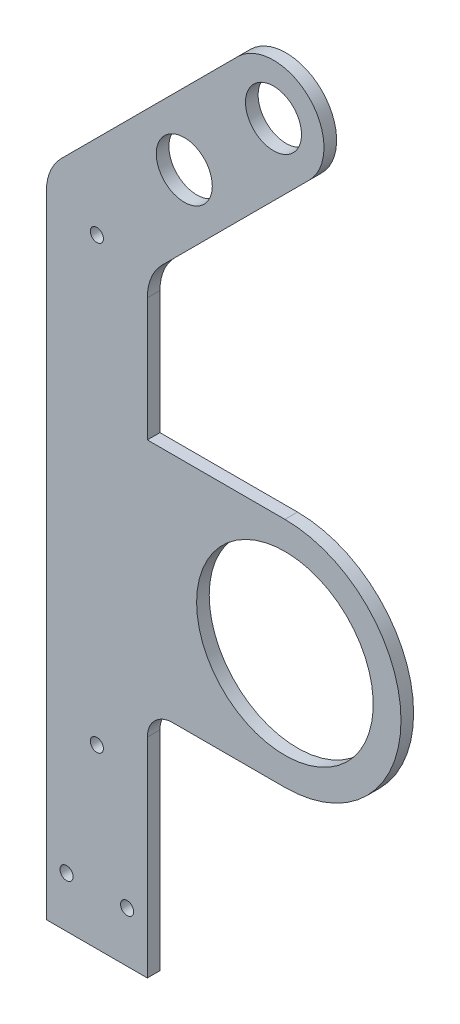
SolidWorks part; units mm, degrees
material "6061 合金"
ref_plane "前视基准面" through (0, 0, 0) normal (0, 0, 1) x (1, 0, 0)
ref_plane "上视基准面" through (0, 0, 0) normal (0, 1, 0) x (1, 0, 0)
ref_plane "右视基准面" through (0, 0, 0) normal (1, 0, 0) x (0, 0, -1)
other "Configuration Table"
sketch "草图1" plane through (0, 0, 0) normal (0, 0, 1) x (1, 0, 0)
  circle A0 centre (0, 0) radius 20
  circle A1 centre (0, 0) radius 11.1
  dimension "D1" = 40
  dimension "D2" = 22.2
extrude "凸台-拉伸1" add sketch "草图1" along normal blind 60 contours A1 | A0 region at (0, 0, 0)
ref_plane "基准面1" through (0, 0, 30) normal (0, 0, 1) x (1, 0, 0)
sketch "草图2" plane through (0, 0, 30) normal (0, 0, 1) x (1, 0, 0)
  line L0 (0, 0) -> (-70, -70) construction
  line L1 (-70, -70) -> (-70, -320) construction
  line L2 (0, -57.3148) -> (0, 49.9409) construction
  line L3 (-56.8582, 0) -> (46.4003, 0) construction
  line L4 (-14.1421, 14.1421) -> (-90, -61.7157)
  line L5 (14.1421, -14.1421) -> (-50, -78.2843)
  line L6 (-90, -61.7157) -> (-90, -320)
  line L7 (-50, -78.2843) -> (-50, -320)
  line L8 (-90, -320) -> (-50, -320)
  circle A2 centre (0, 0) radius 20 construction
  arc A3 (-14.1421, 14.1421) -> (14.1421, -14.1421) centre (0, 0) ccw
  dimension "D1" = 45
  dimension "D2" = 250
  dimension "D3" = 70
  dimension "D4" = 40
  dimension "D5" = 40
extrude "凸台-拉伸2" add sketch "草图2" along normal mid plane 60 contours L7 L8 L6 L4 A3 L5
sketch "草图4" plane through (0, 0, 60) normal (0, 0, 1) x (1, 0, 0)
  line L0 (-90, -61.7157) -> (-90, -320) construction
  line L1 (-90, -290) -> (-50, -290)
  line L2 (-90, -290) -> (-90, -350)
  line L4 (-50, -290) -> (-50, -350)
  line L5 (-50, -78.2843) -> (-50, -320) construction
  line L6 (-90, -320) -> (-50, -320) construction
  arc A0 (-90, -350) -> (-50, -350) centre (-70, -350) ccw
  circle A1 centre (-70, -350) radius 11
  dimension "D3" = 22
  dimension "D1" = 30
  dimension "D2" = 30
extrude "凸台-拉伸3" add sketch "草图4" along normal blind 5
mirror "镜向1" about plane through (0, 0, 30) normal (0, 0, 1) of "凸台-拉伸3"
sketch "草图5" plane through (0, 0, 0) normal (0, 1, 0) x (1, 0, 0)
  line L0 (0, 0) -> (0, -78.0582) construction
ref_plane "基准面2" through (-70, 0, 0) normal (-1, 0, 0) x (0, 0, 1)
sketch "草图7" plane through (-70, 0, 0) normal (-1, 0, 0) x (0, 0, 1)
  line L0 (-34.1239, -350) -> (109.535, -350) construction
sketch "草图8" plane through (0, 0, 60) normal (0, 0, 1) x (1, 0, 0)
  line L0 (0, 0) -> (-70, -70) construction
  circle A0 centre (-35.3553, -35.3553) radius 11.1
  dimension "D1" = 22.2
  dimension "D2" = 50
extrude "切除-拉伸1" cut sketch "草图8" against normal blind 100
fillet "圆角4" radius 20 2 edges at (-90, -61.7157, 30) (-50, -78.2843, 30)
fillet "圆角1" [suppressed] radius 50
fillet "圆角2" [suppressed] radius 3
sketch "草图9" plane through (0, 0, 65) normal (0, 0, 1) x (1, 0, 0)
  circle A0 centre (-70, -350) radius 13
  dimension "D1" = 26
extrude "切除-拉伸2" [suppressed] cut sketch "草图9" against normal blind 0.75
sketch "草图10" plane through (0, 0, -5) normal (0, 0, -1) x (-1, 0, 0)
  circle A0 centre (70, -350) radius 13
  dimension "D1" = 26
extrude "切除-拉伸3" [suppressed] cut sketch "草图10" against normal blind 0.75 contours A0
sketch "草图11" plane through (-90, 0, 0) normal (-1, 0, 0) x (0, 0, 1)
  circle A0 centre (48.5, -118.9949) radius 2.75
  circle A1 centre (48.5, -183.9949) radius 2.75
  circle A2 centre (48.5, -248.9949) radius 2.75
  circle A3 centre (11.5, -248.9949) radius 2.75
  circle A4 centre (11.5, -183.9949) radius 2.75
  circle A5 centre (11.5, -118.9949) radius 2.75
  dimension "D1" = 5.5
extrude "切除-拉伸4" [suppressed] cut sketch "草图11" against normal through all contours A1 | A2 | A0 | A3 | A4 | A5
sketch "草图12" [suppressed] plane through (-90, 0, 0) normal (-1, 0, 0) x (0, 0, 1)
  line L0 (30, -62.0134) -> (30, -339.6946) construction
  line L1 (10, -128.9949) -> (50, -128.9949)
  line L2 (10, -128.9949) -> (10, -173.9949)
  line L3 (10, -173.9949) -> (50, -173.9949)
  line L4 (50, -128.9949) -> (50, -173.9949)
  line L5 (10, -193.9949) -> (50, -193.9949)
  line L6 (10, -193.9949) -> (10, -238.9949)
  line L7 (10, -238.9949) -> (50, -238.9949)
  line L8 (50, -193.9949) -> (50, -238.9949)
  line L9 (10, -258.9949) -> (50, -258.9949)
  line L10 (10, -258.9949) -> (10, -290)
  line L11 (10, -290) -> (50, -290)
  line L12 (50, -258.9949) -> (50, -290)
  line L13 (19.5, -173.9949) -> (40.5, -173.9949)
  line L14 (19.5, -173.9949) -> (19.5, -193.9949)
  line L15 (19.5, -193.9949) -> (40.5, -193.9949)
  line L16 (40.5, -173.9949) -> (40.5, -193.9949)
  line L17 (19.5, -238.9949) -> (40.5, -238.9949)
  line L18 (19.5, -238.9949) -> (19.5, -258.9949)
  line L19 (19.5, -258.9949) -> (40.5, -258.9949)
  line L20 (40.5, -238.9949) -> (40.5, -258.9949)
  line L21 (60, -82.4264) -> (60, -290) construction
  line L22 (0, -290) -> (0, -82.4264) construction
  line L23 (57, -320) -> (3, -320) construction
  circle A0 centre (48.5, -118.9949) radius 2.75 construction
  circle A1 centre (48.5, -183.9949) radius 2.75 construction
  circle A2 centre (48.5, -248.9949) radius 2.75 construction
  dimension "D1" = 10
  dimension "D2" = 10
  dimension "D3" = 10
  dimension "D4" = 8
  dimension "D5" = 10
  dimension "D6" = 10
  dimension "D7" = 10
  dimension "D8" = 30
extrude "减重" [suppressed] cut sketch "草图12" against normal through all contours L0 L1 L2 L3 | L15 L0 L17 L7 L8 L5 | L0 L5 L6 L7 | L19 L0 L11 L12 L9 | L0 L9 L10 L11 | L1 L0 L13 L3 L4
fillet "圆角3" [suppressed] radius 3
sketch "草图13" plane through (0, 0, 60) normal (0, 0, 1) x (1, 0, 0)
  circle A0 centre (0, 0) radius 13
  circle A1 centre (-35.3553, -35.3553) radius 13
  dimension "D1" = 26
  dimension "D2" = 26
extrude "切除-拉伸6" [suppressed] cut sketch "草图13" against normal blind 1.75
sketch "草图14" plane through (0, 0, 0) normal (0, 0, -1) x (-1, 0, 0)
  circle A0 centre (0, 0) radius 13
  circle A1 centre (35.3553, -35.3553) radius 13
  dimension "D1" = 26
  dimension "D2" = 26
extrude "切除-拉伸7" [suppressed] cut sketch "草图14" against normal blind 1.75
sketch "草图15" [suppressed] plane through (0, 0, 0) normal (0, 0, -1) x (-1, 0, 0)
  line L0 (0, 0) -> (70, -350) construction
  line L1 (56.2719, -67.2005) -> (60.1942, -86.8121) construction
  line L2 (70, -350) -> (204.3541, -323.1292) construction
  circle A0 centre (56.2719, -67.2005) radius 2.75
  circle A1 centre (75.2172, -73.6095) radius 2.75
  circle A2 centre (60.1942, -86.8121) radius 2.75
  dimension "D1" = 5.5
  dimension "D2" = 20
  dimension "D3" = 20
  dimension "D4" = 20
  dimension "D5" = 42
  dimension "D6" = 270
extrude "切除-拉伸8" [suppressed] cut sketch "草图15" against normal through all contours A2 | A0 | A1
ref_plane "小腿主干连杆面" through (0, 0, 0) normal (0.9806, -0.1961, 0) x (0, 0, -1)
ref_plane "小腿主干对称面" through (0, 0, 30) normal (0, 0, -1) x (-1, 0, 0)
sketch "草图16" plane through (0, 0, 60) normal (0, 0, 1) x (1, 0, 0)
  line L0 (0, 0) -> (-70, -350)
  line L1 (-35.3553, -35.3553) -> (0, 0)
sketch "草图17" plane through (0, 0, 60) normal (0, 0, 1) x (1, 0, 0)
  line L0 (0, 0) -> (-70, -350) construction
  line L1 (118.6974, 32.5948) -> (32.9122, -396.3312) construction
  line L2 (92.7764, -97.0102) -> (24.1357, -83.2821)
  line L3 (73.1648, -195.0683) -> (4.5241, -181.3401)
  circle A0 centre (24.1357, -83.2821) radius 46
  circle A1 centre (4.5241, -181.3401) radius 46
  dimension "D3" = 92
  dimension "D4" = 92
  dimension "D1" = 110
  dimension "D2" = 70
  dimension "D5" = 180
  dimension "D6" = 280
sketch "草图18" plane through (0, 0, 60) normal (0, 0, 1) x (1, 0, 0)
  line L1 (14.1421, -14.1421) -> (-44.1421, -72.4264) construction
  line L3 (14.1421, -14.1421) -> (-44.1421, -72.4264)
  line L4 (16.784, -10.8765) -> (56.6627, -50.7551)
  line L5 (-50, -129.2821) -> (24.1357, -129.2821)
  line L10 (-90, -290) -> (-50, -290)
  line L11 (-50, -290) -> (-50, -86.5685)
  line L12 (-44.1421, -72.4264) -> (14.1421, -14.1421)
  line L13 (-14.1421, 14.1421) -> (-84.1421, -55.8579)
  line L14 (-90, -70) -> (-90, -290)
  line L16 (-50, -129.2821) -> (-50, -86.5685)
  line L17 (-44.1421, -72.4264) -> (14.1421, -14.1421)
  circle A0 centre (24.1357, -83.2821) radius 46 construction
  arc A1 (14.1421, -14.1421) -> (-14.1421, 14.1421) centre (0, 0) ccw construction
  arc A2 (14.1421, -14.1421) -> (-14.1421, 14.1421) centre (0, 0) ccw
  arc A3 (14.1421, -14.1421) -> (16.784, -10.8765) centre (0, 0) ccw
  arc A4 (24.1357, -129.2821) -> (56.6627, -50.7551) centre (24.1357, -83.2821) ccw
  circle A5 centre (24.1357, -83.2821) radius 35
  arc A9 (-84.1421, -55.8579) -> (-90, -70) centre (-70, -70) ccw
  arc A10 (-84.1421, -55.8579) -> (-90, -70) centre (-70, -70) ccw
  arc A11 (-44.1421, -72.4264) -> (-50, -86.5685) centre (-30, -86.5685) ccw
  arc A12 (-44.1421, -72.4264) -> (-50, -86.5685) centre (-30, -86.5685) ccw
  line M14 (-50, -290) -> (-50, -86.5685)
  line M15 (-44.1421, -72.4264) -> (14.1421, -14.1421)
  arc M16 (14.1421, -14.1421) -> (-14.1421, 14.1421) centre (0, 0) ccw
  arc M22 (-50, -86.5685) -> (-44.1421, -72.4264) centre (-30, -86.5685) cw
  dimension "D2" = 70
  dimension "D1" = 0
extrude "凸台-拉伸4" add sketch "草图18" against normal blind 5 from offset 25 contours L5 A4 L4 A5 M16 M15 M22 M14 region at (16.8604, -13.6397, 60) offset against normal yes
sketch "草图19" plane through (0, 0, 0) normal (0, 0, -1) x (-1, 0, 0)
  line L0 (50, -86.5685) -> (50, -290) construction
  line L1 (50, -135.3401) -> (50, -227.3401)
  line L2 (-4.5241, -135.3401) -> (50, -135.3401)
  line L3 (-4.5241, -227.3401) -> (50, -227.3401)
  circle A0 centre (-4.5241, -181.3401) radius 46 construction
  arc A1 (-4.5241, -135.3401) -> (-4.5241, -227.3401) centre (-4.5241, -181.3401) ccw
  circle A2 centre (-4.5241, -181.3401) radius 35
  dimension "D1" = 70
extrude "凸台-拉伸5" add sketch "草图19" against normal blind 5 from offset 25 offset against normal yes
fillet "圆角5" radius 10 2 edges at (-50, -227.3401, 27.5) (-50, -129.2821, 32.5)
sketch "草图21" plane through (0, 0, 65) normal (0, 0, 1) x (1, 0, 0)
  line L0 (-70, -350) -> (-70, -6.9331) construction
  circle A0 centre (-70, -75) radius 2.6
  circle A1 centre (-70, -250) radius 2.6
  circle A2 centre (-58, -300) radius 2.6
  circle A3 centre (-82, -300) radius 2.6
  dimension "D1" = 5.2
  dimension "D2" = 12
  dimension "D3" = 50
  dimension "D4" = 100
  dimension "D5" = 175
extrude "切除-拉伸9" cut sketch "草图21" against normal through all both and the other way through all
sketch "草图22" plane through (-90, 0, 0) normal (-1, 0, 0) x (0, 0, 1)
  line L0 (-5, -350) -> (-5, -370) construction
  line L5 (-5, -404.8194) -> (25, -404.8194)
  line L6 (-5, -404.8194) -> (-5, 64.9179)
  line L7 (-5, 64.9179) -> (25, 64.9179)
  line L8 (25, -404.8194) -> (25, 64.9179)
  line L10 (65, -370) -> (30, -370)
  line L11 (65, -370) -> (65, 61.088)
  line L12 (65, 61.088) -> (30, 61.088)
  line L13 (30, -370) -> (30, 61.088)
  dimension "D1" = 35
  dimension "D2" = 5
extrude "切除-拉伸10" cut sketch "草图22" against normal through all both contours L8 L7 L6 L5 | L13 L12 L11 L10
